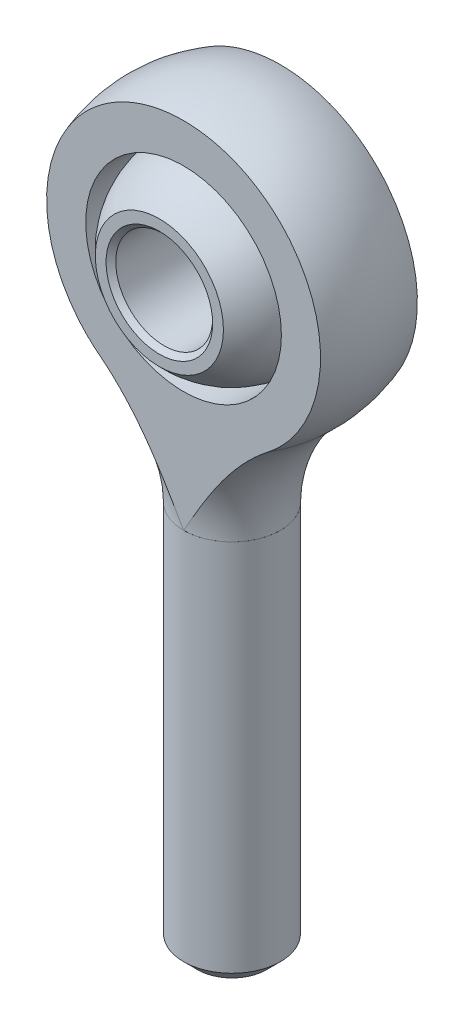
SolidWorks part; units mm, degrees
ref_plane "Front" through (0, 0, 0) normal (0, 0, 1) x (1, 0, 0)
ref_plane "Top" through (0, 0, 0) normal (0, 1, 0) x (1, 0, 0)
ref_plane "Right" through (0, 0, 0) normal (1, 0, 0) x (0, 0, -1)
sketch "Sketch1" plane through (0, 0, 0) normal (0, 0, 1) x (1, 0, 0)
  line L0 (0, 0) -> (0, -25.4)
  line L1 (0, -25.4) -> (3.175, -25.4)
  line L2 (3.175, -25.4) -> (3.175, 0)
  line L3 (3.175, 0) -> (0, 0)
  line L5 (0, 23.8125) -> (0, 0) construction
  line L6 (0, 23.8125) -> (9.525, 23.8125) construction
  line L7 (9.525, 23.8125) -> (9.525, 14.2875) construction
  line L8 (-3.175, -25.4) -> (-3.175, 0) construction
  line L9 (3.2732, -25.3433) -> (3.2732, -26.2501)
  line L10 (3.2732, -26.2501) -> (2.4879, -25.7967)
  line L11 (2.586, -25.8534) -> (2.586, -25.74)
  line L12 (2.4879, -25.7967) -> (3.2732, -25.3433)
  line L13 (3.2241, -25.3717) -> (3.2241, -26.2218)
  line L14 (3.2732, -25.7967) -> (3.175, -25.7967)
  line L15 (3.175, -25.4) -> (3.175, -26.1934)
  line L16 (2.4879, -25.7967) -> (2.586, -25.7967)
  arc A0 (6.3827, 7.2174) -> (0, 23.8125) centre (0, 14.2875) ccw construction
  circle A1 centre (0, 14.2875) radius 3.175 construction
  circle A2 centre (0, 14.2875) radius 6.35 construction
  circle A3 centre (0, 14.2875) radius 6.4135 construction
  arc A4 (3.175, 0) -> (6.3827, 7.2174) centre (12.8984, 0) cw construction
  point P24 (0, 20.6375)
  point P26 (3.175, -25.7967)
  point P28 (3.2241, -25.7967)
  dimension "A" = 6.35
  dimension "Ball Dia" = 12.7
  dimension "B" = 19.05
  dimension "D1" = 12.827
  dimension "D" = 39.6875
  dimension "E" = 25.4
  dimension "Thread Dia" = 6.35
  dimension "D2" = 60
  dimension "Pitch" = 0.9068
  dimension "D4" = 0.1133
sketch "Sketch2" plane through (0, 0, 0) normal (1, 0, 0) x (0, 0, -1)
  line L0 (3.175, 14.2875) -> (-3.175, 14.2875)
  line L1 (3.175, 15.0498) -> (0, 14.2875) construction
  line L2 (3.175, 13.5252) -> (0, 14.2875) construction
  line L6 (4.7625, 14.2875) -> (-4.7625, 14.2875)
  line L7 (0, 11.1125) -> (0, 17.4625)
  line L8 (0, 23.8125) -> (0, 0) construction
  line L9 (0, 17.4625) -> (0, 11.1125) construction
  circle A0 centre (0, 14.2875) radius 6.35
  circle A1 centre (0, 14.2875) radius 9.525
  point P4 (0, 14.2875)
  point P7 (0, 20.6375)
  point P9 (0, 7.9375)
  point P14 (0, 14.2875)
  point P18 (0, 14.2875)
  point P23 (9.525, 14.2875)
  point P25 (-9.525, 14.2875)
  dimension "OAWidth" = 6.35
  dimension "Swivel" = 27
  dimension "BallWidth" = 9.525
sketch "Sketch15" plane through (0, 0, 0) normal (0, 0, 1) x (1, 0, 0)
  line L0 (0, 23.8125) -> (0, 0) construction
  line L1 (9.525, 23.8125) -> (-9.525, 23.8125)
  line L2 (9.525, 23.8125) -> (9.525, 0)
  line L3 (9.525, 0) -> (-9.525, 0)
  line L4 (-9.525, 23.8125) -> (-9.525, 0)
  line L5 (3.175, 0) -> (0, 0) construction
  point P5 (0, 23.8125)
sketch "Sketch14" plane through (0, 0, 0) normal (0, 0, 1) x (1, 0, 0)
  line L1 (0, 0) -> (0, -25.4) construction
  line L2 (0, -25.4) -> (3.175, -25.4) construction
  line L3 (3.175, -25.4) -> (3.175, 0) construction
  line L5 (0, 0) -> (0, -25.4)
  line L6 (0, -25.4) -> (3.175, -25.4)
  line L7 (3.175, -25.4) -> (3.175, 0)
  line L8 (3.175, 0) -> (0, 0) construction
  line L9 (3.175, 0) -> (0, 0)
revolve "Revolve4" add sketch "Sketch14" angle 360 about L0
sketch "Sketch21" plane through (0, 0, 0) normal (0, 0, 1) x (1, 0, 0)
  line L0 (0, 23.8125) -> (0, 0) construction
  line L1 (3.175, 0) -> (0, 0) construction
  line L2 (0, 23.8125) -> (0, 0)
  line L3 (3.175, 0) -> (0, 0)
  arc A0 (6.3827, 7.2174) -> (3.175, 0) centre (12.8984, 0) ccw construction
  arc A1 (6.3827, 7.2174) -> (0, 23.8125) centre (0, 14.2875) ccw construction
  arc A2 (6.3827, 7.2174) -> (3.175, 0) centre (12.8984, 0) ccw
  arc A3 (6.3827, 7.2174) -> (0, 23.8125) centre (0, 14.2875) ccw
revolve "Revolve5" add sketch "Sketch21" angle 360 about L0
sketch "Sketch24" plane through (0, 0, 0) normal (1, 0, 0) x (0, 0, -1)
  line L0 (3.175, 14.2875) -> (3.175, 23.8125)
  line L1 (3.175, 23.8125) -> (9.525, 23.8125)
  line L2 (9.525, 0) -> (9.525, 23.8125)
  line L3 (3.175, 14.2875) -> (3.175, 0.635)
  line L4 (3.175, 0.635) -> (3.175, 0)
  line L5 (3.175, 0) -> (9.525, 0)
  line L6 (0, 23.8125) -> (0, 0) construction
  line L7 (0, 23.8125) -> (0, 0) construction
  line L8 (-3.175, 0) -> (-9.525, 0)
  line L9 (-3.175, 0.635) -> (-3.175, 0)
  line L10 (-3.175, 14.2875) -> (-3.175, 0.635)
  line L11 (-9.525, 0) -> (-9.525, 23.8125)
  line L12 (-3.175, 23.8125) -> (-9.525, 23.8125)
  line L13 (-3.175, 14.2875) -> (-3.175, 23.8125)
  dimension "D1" = 0.635
extrude "Cut-Extrude10" cut sketch "Sketch24" against normal through all both and the other way through all
sketch "Sketch17" plane through (0, 0, 0) normal (0, 0, 1) x (1, 0, 0)
  circle A2 centre (0, 14.2875) radius 6.4135 construction
  circle A3 centre (0, 14.2875) radius 6.4135
extrude "Cut-Extrude9" cut sketch "Sketch17" against normal through all both and the other way through all
sketch "Sketch7" plane through (0, 0, 0) normal (0, 0, 1) x (1, 0, 0)
  line L0 (0, 20.6375) -> (0, 7.9375)
  line L1 (0, 23.8125) -> (0, 0) construction
  line L2 (0, 0) -> (0, 7.9375) construction
  arc A0 (0, 7.9375) -> (0, 20.6375) centre (0, 14.2875) ccw
  circle A1 centre (0, 14.2875) radius 6.35 construction
revolve "Revolve3" add sketch "Sketch7" angle 360 about L2
sketch "Sketch10" plane through (0, 0, 0) normal (0, 0, 1) x (1, 0, 0)
  circle A0 centre (0, 14.2875) radius 3.175 construction
  circle A1 centre (0, 14.2875) radius 3.175
extrude "Cut-Extrude4" cut sketch "Sketch10" against normal through all and the other way through all
sketch "Sketch22" plane through (0, 0, 0) normal (0, 0, 1) x (1, 0, 0)
  line L0 (-9.525, 23.8125) -> (-9.525, 0) construction
  line L1 (9.525, 0) -> (-9.525, 0) construction
  line L2 (9.525, 23.8125) -> (9.525, 0) construction
  line L3 (9.525, 23.8125) -> (-9.525, 23.8125) construction
  line L4 (-9.525, 23.8125) -> (-9.525, 0)
  line L5 (9.525, 0) -> (-9.525, 0)
  line L6 (9.525, 23.8125) -> (9.525, 0)
  line L7 (9.525, 23.8125) -> (-9.525, 23.8125)
extrude "Cut-Extrude7" cut sketch "Sketch22" against normal through all from vertex starting at point (0, 14.2875, -4.7625)
sketch "Sketch23" plane through (0, 0, 0) normal (0, 0, 1) x (1, 0, 0)
  line L0 (-9.525, 23.8125) -> (-9.525, 0) construction
  line L1 (9.525, 0) -> (-9.525, 0) construction
  line L2 (9.525, 23.8125) -> (9.525, 0) construction
  line L3 (9.525, 23.8125) -> (-9.525, 23.8125) construction
  line L4 (-9.525, 23.8125) -> (-9.525, 0)
  line L5 (9.525, 0) -> (-9.525, 0)
  line L6 (9.525, 23.8125) -> (9.525, 0)
  line L7 (9.525, 23.8125) -> (-9.525, 23.8125)
extrude "Cut-Extrude8" cut sketch "Sketch23" along normal through all from vertex starting at point (0, 14.2875, 4.7625)
chamfer "Chamfer1" distance 0.9068 angle 45 1 edges at (-3.175, -25.4, 0)
chamfer "Chamfer2" distance 0.3175 angle 45 2 edges at (3.175, 14.2875, 4.7625) (3.175, 14.2875, -4.7625)
sketch "Sketch18" [suppressed] plane through (0, -25.4, 0) normal (0, -1, 0) x (1, 0, 0)
  circle A0 centre (0, 0) radius 3.175 construction
  circle A1 centre (0, 0) radius 3.175
curve "Helix/Spiral1" [suppressed] pitch 0.9068 height 26.3068 turns 29.0112
sketch "Sketch19" [suppressed] plane through (0, 0, 0) normal (0, 0, 1) x (1, 0, 0)
  line L0 (2.586, -25.8534) -> (2.586, -25.74) construction
  line L1 (2.4879, -25.7967) -> (3.2732, -25.3433) construction
  line L2 (3.2732, -26.2501) -> (2.4879, -25.7967) construction
  line L3 (3.2241, -25.3717) -> (3.2241, -26.2218) construction
  line L4 (2.586, -25.8534) -> (2.586, -25.74)
  line L5 (2.586, -25.74) -> (3.2241, -25.3717)
  line L6 (3.2241, -26.2218) -> (2.586, -25.8534)
  line L7 (3.2241, -25.3717) -> (3.2241, -26.2218)
sweep "Cut-Sweep1" [suppressed] cut profiles "Sketch19" path "Helix/Spiral1"
ref_plane "Plane1" [suppressed] through (0, 0, 0) normal (0, 1, 0) x (1, 0, 0)
sketch "Sketch20" [suppressed] plane through (0, 0, 0) normal (0, 1, 0) x (1, 0, 0)
  circle A0 centre (0, 0) radius 3.175
extrude "Boss-Extrude2" [suppressed] add sketch "Sketch20" against normal through all draft 60
combine bodies "Combine1" [suppressed] operation type add bodies to combine 130 133
equation "\"D1@Sketch1\"=\"Ball Dia@Sketch1\"*1.01"
equation "\"D1\"= \"A@Sketch1\" / 20"
equation "\"D3\"= \"E@Sketch1\" + .2"
equation "\"D4@Sketch1\"=\"Pitch@Sketch1\"/8"
equation "\"D1@Chamfer1\"=\"Pitch@Sketch1\""
equation "\"D4@Helix/Spiral1\"=\"Pitch@Sketch1\""
equation "\"D3@Helix/Spiral1\"=\"E@Sketch1\"+\"Pitch@Sketch1\""
equation "\"D1@Chamfer2\"=\"A@Sketch1\"/20"
equation "\"D1@Sketch24\"=(\"OAWidth@Sketch2\"/2)/5"
